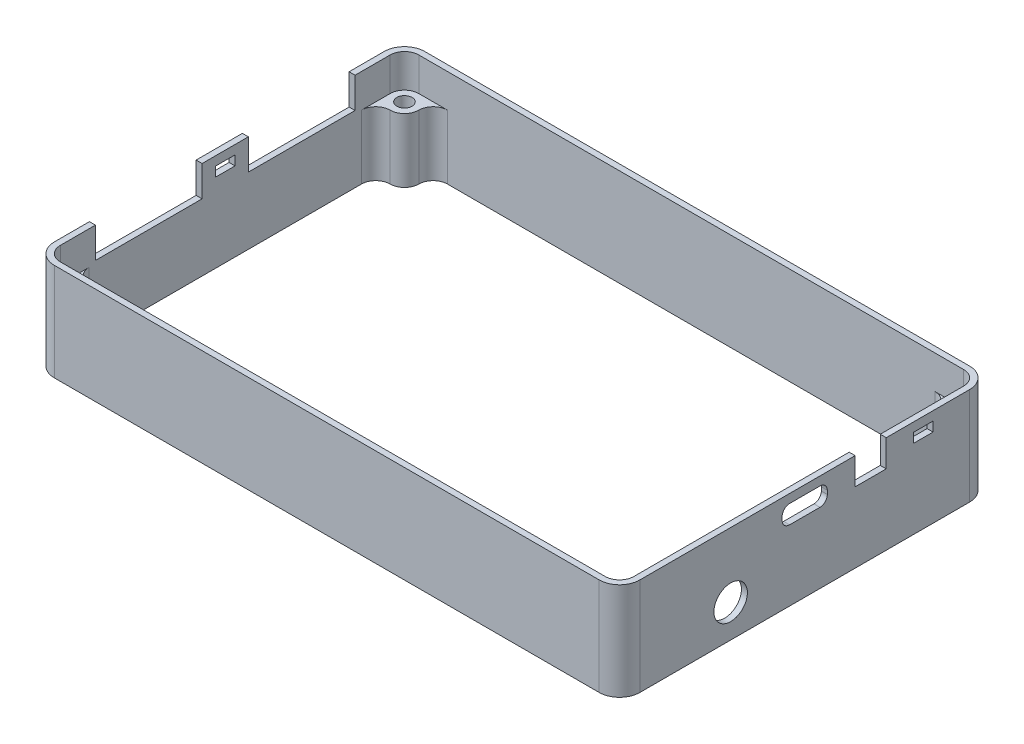
SolidWorks part; units mm, degrees
ref_plane "Front Plane" through (0, 0, 0) normal (0, 0, 1) x (1, 0, 0)
ref_plane "Top Plane" through (0, 0, 0) normal (0, 1, 0) x (1, 0, 0)
ref_plane "Right Plane" through (0, 0, 0) normal (1, 0, 0) x (0, 0, -1)
sketch "pcb" plane through (0, 0, 0) normal (0, 1, 0) x (1, 0, 0)
  line L0 (-14, -27.5) -> (-42, -27.5) construction
  line L1 (-57, -37.5) -> (57, -37.5)
  line L2 (-60, -34.5) -> (-60, 34.5)
  line L3 (-57, 37.5) -> (57, 37.5)
  line L4 (60, -34.5) -> (60, 34.5)
  line L5 (-60, -37.5) -> (60, 37.5) construction
  line L6 (-60, 37.5) -> (60, -37.5) construction
  line L7 (-14, -27.5) -> (14, -27.5) construction
  line L8 (14, -27.5) -> (42, -27.5) construction
  line L9 (-42, -27.5) -> (-60, -27.5) construction
  line L10 (42, -27.5) -> (60, -27.5) construction
  line L11 (-60, 0) -> (60, 0) construction
  line L13 (2.43, 12.5075) -> (10.05, 12.5075)
  line L14 (2.43, 12.5075) -> (2.43, 9.9675)
  line L15 (2.43, 9.9675) -> (10.05, 9.9675)
  line L16 (10.05, 12.5075) -> (10.05, 9.9675)
  arc A0 (-57, -37.5) -> (-60, -34.5) centre (-57, -34.5) cw
  arc A1 (57, -37.5) -> (60, -34.5) centre (57, -34.5) ccw
  arc A2 (57, 37.5) -> (60, 34.5) centre (57, 34.5) cw
  arc A3 (-60, 34.5) -> (-57, 37.5) centre (-57, 34.5) cw
  circle A4 centre (-57, 34.5) radius 1.6
  circle A5 centre (57, 34.5) radius 1.6
  circle A6 centre (57, -34.5) radius 1.6
  circle A7 centre (-57, -34.5) radius 1.6
  circle A8 centre (-42, -27.5) radius 5.5
  circle A9 centre (-14, -27.5) radius 5.5
  circle A10 centre (14, -27.5) radius 5.5
  circle A11 centre (42, -27.5) radius 5.5
  circle A12 centre (-42, 27.5) radius 5.5
  circle A13 centre (-14, 27.5) radius 5.5
  circle A14 centre (14, 27.5) radius 5.5
  circle A15 centre (42, 27.5) radius 5.5
  point P0 (0, 0)
  dimension "D3" = 3
  dimension "D4" = 3
  dimension "D5" = 3
  dimension "D6" = 3
  dimension "D7" = 3.2
  dimension "D9" = 11
  dimension "D10" = 18
  dimension "D1" = 120
  dimension "D2" = 75
  dimension "D8" = 10
  dimension "D11" = 62.43
  dimension "D12" = 47.4675
  dimension "D13" = 2.54
  dimension "D14" = 7.62
sketch "Sketch3" plane through (0, 0, 0) normal (0, 0, 1) x (1, 0, 0)
  line L0 (0, 0) -> (0, 1.6) construction
  line L1 (-57, 0) -> (57, 0) construction
  line L2 (0, 1.6) -> (0, 7) construction
  line L3 (0, 7) -> (0, 8.6) construction
  line L4 (0, 0) -> (0, -13.4) construction
  line L5 (0, -13.4) -> (0, -16.4) construction
  dimension "D1" = 1.6
  dimension "D2" = 3
  dimension "D3" = 13.4
  dimension "D4" = 5.4
  dimension "D5" = 1.6
  dimension "D6" = 25
sketch "Sketch2" plane through (0, 0, 0) normal (0, 1, 0) x (1, 0, 0)
  line L0 (-60, -34.5) -> (-60, 34.5) construction
  line L1 (-57, -37.5) -> (57, -37.5) construction
  line L2 (60, -34.5) -> (60, 34.5) construction
  line L3 (-57, 37.5) -> (57, 37.5) construction
  line L4 (-60, -34.5) -> (-60, 34.5)
  line L5 (-57, -37.5) -> (57, -37.5)
  line L6 (60, -34.5) -> (60, 34.5)
  line L7 (-57, 37.5) -> (57, 37.5)
  line L8 (-61.25, -34.5) -> (-61.25, 34.5)
  line L9 (-57, -38.75) -> (57, -38.75)
  line L10 (61.25, -34.5) -> (61.25, 34.5)
  line L11 (-57, 38.75) -> (57, 38.75)
  arc A0 (-57, 37.5) -> (-60, 34.5) centre (-57, 34.5) ccw construction
  arc A1 (-60, -34.5) -> (-57, -37.5) centre (-57, -34.5) ccw construction
  arc A2 (57, -37.5) -> (60, -34.5) centre (57, -34.5) ccw construction
  arc A3 (60, 34.5) -> (57, 37.5) centre (57, 34.5) ccw construction
  arc A4 (-57, 37.5) -> (-60, 34.5) centre (-57, 34.5) ccw
  arc A5 (-60, -34.5) -> (-57, -37.5) centre (-57, -34.5) ccw
  arc A6 (57, -37.5) -> (60, -34.5) centre (57, -34.5) ccw
  arc A7 (60, 34.5) -> (57, 37.5) centre (57, 34.5) ccw
  arc A8 (-57, 38.75) -> (-61.25, 34.5) centre (-57, 34.5) ccw
  arc A9 (-61.25, -34.5) -> (-57, -38.75) centre (-57, -34.5) ccw
  arc A10 (57, -38.75) -> (61.25, -34.5) centre (57, -34.5) ccw
  arc A11 (61.25, 34.5) -> (57, 38.75) centre (57, 34.5) ccw
  dimension "D1" = 1.25
extrude "Walls" add sketch "Sketch2" against normal up to vertex (13.4 mm away) and the other way up to vertex (7 mm away) up to point (0, -13.4, 0) other way up to point (0, 7, 0)
sketch "Sketch11" plane through (0, 0, 0) normal (0, 1, 0) x (1, 0, 0)
  line L0 (-60, -34.5) -> (-60, -31.5)
  line L1 (-60, -34.5) -> (-60, 34.5) construction
  line L2 (-60, -31.5) -> (-54, -31.5)
  line L3 (-54, -31.5) -> (-54, -37.5)
  line L4 (-57, -37.5) -> (57, -37.5) construction
  line L5 (-54, -37.5) -> (-57, -37.5)
  line L6 (-57, 37.5) -> (-54, 37.5)
  line L7 (-57, 37.5) -> (57, 37.5) construction
  line L8 (-54, 37.5) -> (-54, 31.5)
  line L9 (-54, 31.5) -> (-60, 31.5)
  line L10 (-60, 31.5) -> (-60, 34.5)
  line L11 (60, -31.5) -> (54, -31.5)
  line L12 (60, -34.5) -> (60, 34.5) construction
  line L13 (54, -31.5) -> (54, -37.5)
  line L14 (54, -37.5) -> (57, -37.5)
  line L15 (60, -31.5) -> (60, -34.5)
  line L16 (57, 37.5) -> (54, 37.5)
  line L17 (54, 37.5) -> (54, 31.5)
  line L18 (54, 31.5) -> (60, 31.5)
  line L19 (60, 31.5) -> (60, 34.5)
  arc A0 (-60, -34.5) -> (-57, -37.5) centre (-57, -34.5) ccw construction
  arc A1 (-60, -34.5) -> (-57, -37.5) centre (-57, -34.5) ccw
  arc A2 (-57, 37.5) -> (-60, 34.5) centre (-57, 34.5) ccw construction
  arc A3 (-57, 37.5) -> (-60, 34.5) centre (-57, 34.5) ccw
  circle A4 centre (-57, 34.5) radius 1.6 construction
  circle A5 centre (-57, 34.5) radius 1.6
  circle A6 centre (-57, -34.5) radius 1.6 construction
  circle A7 centre (-57, -34.5) radius 1.6
  arc A8 (57, -37.5) -> (60, -34.5) centre (57, -34.5) ccw construction
  arc A9 (57, -37.5) -> (60, -34.5) centre (57, -34.5) ccw
  circle A10 centre (57, -34.5) radius 1.6 construction
  circle A11 centre (57, -34.5) radius 1.6
  arc A12 (60, 34.5) -> (57, 37.5) centre (57, 34.5) ccw construction
  arc A13 (60, 34.5) -> (57, 37.5) centre (57, 34.5) ccw
  circle A14 centre (57, 34.5) radius 1.6 construction
  circle A15 centre (57, 34.5) radius 1.6
  dimension "D1" = 6
  dimension "D2" = 6
  dimension "D3" = 6
  dimension "D4" = 6
extrude "Boss-Extrude4" add sketch "Sketch11" against normal up to surface (13.4 mm away) up to face at (0, -13.4, 0)
fillet "Fillet1" radius 3 12 edges at (60, -6.7, -31.5) (54, -6.7, -37.5) (-54, -6.7, -37.5) (-60, -6.7, -31.5) (-54, -6.7, 37.5) (-60, -6.7, 31.5) (54, -6.7, 37.5) (60, -6.7, 31.5) (54, -6.7, 31.5) (-54, -6.7, 31.5) (-54, -6.7, -31.5) (54, -6.7, -31.5)
sketch "Sketch8" plane through (61.25, 0, 0) normal (1, 0, 0) x (0, 0, -1)
  line L0 (0, 1.6) -> (0, 7) construction
  line L1 (-3.17, 1.57) -> (3.17, 1.57)
  line L2 (-4.47, 2.87) -> (-4.47, 3.63)
  line L3 (-3.17, 4.93) -> (3.17, 4.93)
  line L4 (4.47, 2.87) -> (4.47, 3.63)
  line L5 (-4.47, 1.57) -> (4.47, 4.93) construction
  line L6 (-4.47, 4.93) -> (4.47, 1.57) construction
  line L8 (0, 0) -> (0, 1.6) construction
  line L9 (0, 0) -> (0, 1.6) construction
  line L11 (16.8, 1.6) -> (10.8, 1.6)
  line L12 (16.8, 1.6) -> (16.8, 6.82)
  line L13 (16.8, 6.82) -> (10.8, 6.82)
  line L14 (10.8, 1.6) -> (10.8, 6.82)
  line L15 (-37.5, 0) -> (37.5, 0) construction
  line L16 (0, 0) -> (0, -13.4) construction
  line L18 (23, 4.87) -> (26.6, 4.87)
  line L19 (23, 4.87) -> (23, 3.37)
  line L20 (23, 3.37) -> (26.6, 3.37)
  line L21 (26.6, 4.87) -> (26.6, 3.37)
  arc A0 (3.17, 4.93) -> (4.47, 3.63) centre (3.17, 3.63) cw
  arc A1 (3.17, 1.57) -> (4.47, 2.87) centre (3.17, 2.87) ccw
  arc A2 (-3.17, 1.57) -> (-4.47, 2.87) centre (-3.17, 2.87) cw
  arc A3 (-4.47, 3.63) -> (-3.17, 4.93) centre (-3.17, 3.63) cw
  circle A4 centre (-15.5, -6.55) radius 3.25
  point P0 (0, 3.25)
  point P10 (13.8, 1.6)
  dimension "D4" = 1.3
  dimension "D5" = 1.3
  dimension "D6" = 1.3
  dimension "D7" = 1.3
  dimension "D11" = 6.5
  dimension "D1" = 3.36
  dimension "D2" = 8.94
  dimension "D3" = 3.25
  dimension "D8" = 13.8
  dimension "D9" = 6
  dimension "D10" = 5.22
  dimension "D12" = 6.55
  dimension "D13" = 15.5
  dimension "D14" = 1.5
  dimension "D15" = 3.6
  dimension "D16" = 1.77
  dimension "D17" = 9.2
extrude "Cut-Extrude3" cut sketch "Sketch8" along direction (1, 0, 0) on the side against the normal up to surface (1.25 mm away) up to face at (60, -1.6, 0)
sketch "Sketch10" plane through (-61.25, 0, 0) normal (-1, 0, 0) x (0, 0, 1)
  line L0 (-34.5, 7) -> (34.5, 7) construction
  line L1 (5.84, 1.6) -> (26.16, 1.6)
  line L2 (5.84, 1.6) -> (5.84, 7)
  line L3 (5.84, 7) -> (26.16, 7)
  line L4 (26.16, 1.6) -> (26.16, 7)
  line L6 (-5.84, 1.6) -> (-26.16, 1.6)
  line L7 (-5.84, 1.6) -> (-5.84, 7)
  line L8 (-5.84, 7) -> (-26.16, 7)
  line L9 (-26.16, 1.6) -> (-26.16, 7)
  line L10 (0, 0) -> (0, 1.6) construction
  line L15 (0, 0) -> (0, 1.6) construction
  line L16 (-5.84, 1.6) -> (0, 1.6) construction
  line L17 (0, 1.6) -> (5.84, 1.6) construction
  line L22 (-1.8, 4.87) -> (1.8, 4.87)
  line L23 (-1.8, 4.87) -> (-1.8, 3.37)
  line L24 (-1.8, 3.37) -> (1.8, 3.37)
  line L25 (1.8, 4.87) -> (1.8, 3.37)
  point P10 (0, 3.37)
  dimension "D1" = 20.32
  dimension "D2" = 20.32
  dimension "D3" = 11.68
  dimension "D4" = 3.6
  dimension "D5" = 1.5
  dimension "D6" = 1.77
extrude "Cut-Extrude4" cut sketch "Sketch10" against normal up to next
other "Move Face3" flip direction yes face at (60.625, 4.12, -23) face at (60.625, 4.87, -24.8) face at (60.625, 4.12, -26.6) face at (60.625, 3.37, -24.8) offset 0.25 parameters "D1"=0.25
other "Move Face4" flip direction yes face at (60, -6.55, 12.25) face at (60.625, 2.0854, 3.9546) face at (60.625, 3.25, 4.47) face at (60.625, 4.4146, 3.9546) face at (60.625, 4.93, 0) face at (60.625, 2.0854, -3.9546) face at (60.625, 1.57, 0) face at (60.625, 3.25, -4.47) face at (60.625, 4.4146, -3.9546) face at (60.625, 1.6, -13.8) face at (60.625, 4.21, -16.8) face at (60.625, 4.21, -10.8) face at (60.625, 6.82, -13.8) offset 0.25 parameters "D1"=0.25
other "Move Face1" flip direction yes face at (-60.625, 4.3, 26.16) face at (-60.625, 1.6, 16) face at (-60.625, 4.3, 5.84) face at (-60.625, 4.3, -26.16) face at (-60.625, 1.6, -16) face at (-60.625, 4.3, -5.84) offset 1 parameters "D1"=1
other "Move Face2" flip direction yes face at (-60.625, 4.12, -1.8) face at (-60.625, 4.87, 0) face at (-60.625, 3.37, 0) face at (-60.625, 4.12, 1.8) offset 0.25 parameters "D1"=0.25
sketch "Sketch4" plane through (0, -13.4, 0) normal (0, -1, 0) x (1, 0, 0)
  line L4 (-57, -38.75) -> (57, -38.75)
  line L5 (61.25, -34.5) -> (61.25, 34.5)
  line L6 (57, 38.75) -> (-57, 38.75)
  line L7 (-61.25, 34.5) -> (-61.25, -34.5)
  line L8 (-57, -38.75) -> (57, -38.75)
  line L9 (61.25, -34.5) -> (61.25, 34.5)
  line L10 (57, 38.75) -> (-57, 38.75)
  line L11 (-61.25, 34.5) -> (-61.25, -34.5)
  circle A0 centre (57, -34.5) radius 2.15
  circle A1 centre (-57, -34.5) radius 2.15
  circle A2 centre (-57, 34.5) radius 2.15
  circle A3 centre (57, 34.5) radius 2.15
  arc A4 (-61.25, -34.5) -> (-57, -38.75) centre (-57, -34.5) ccw
  arc A5 (57, -38.75) -> (61.25, -34.5) centre (57, -34.5) ccw
  arc A6 (61.25, 34.5) -> (57, 38.75) centre (57, 34.5) ccw
  arc A7 (-57, 38.75) -> (-61.25, 34.5) centre (-57, 34.5) ccw
  arc A8 (-61.25, -34.5) -> (-57, -38.75) centre (-57, -34.5) ccw
  arc A9 (57, -38.75) -> (61.25, -34.5) centre (57, -34.5) ccw
  arc A10 (61.25, 34.5) -> (57, 38.75) centre (57, 34.5) ccw
  arc A11 (-57, 38.75) -> (-61.25, 34.5) centre (-57, 34.5) ccw
  dimension "D2" = 4.3
  dimension "D1" = 0
extrude "Bottom Lid" add sketch "Sketch4" along normal blind 3 separate body
sketch "Sketch5" plane through (0, 7, 0) normal (0, 1, 0) x (1, 0, 0)
  line L0 (2.43, 12.5075) -> (2.43, 9.9675) construction
  line L1 (2.43, 9.9675) -> (10.05, 9.9675) construction
  line L2 (2.43, 12.5075) -> (10.05, 12.5075) construction
  line L3 (10.05, 12.5075) -> (10.05, 9.9675) construction
  line L4 (57, 38.75) -> (-57, 38.75)
  line L5 (61.25, -34.5) -> (61.25, 34.5)
  line L6 (-57, -38.75) -> (57, -38.75)
  line L7 (-61.25, 34.5) -> (-61.25, -34.5)
  line L12 (57, 38.75) -> (-57, 38.75)
  line L13 (61.25, -34.5) -> (61.25, 34.5)
  line L14 (-57, -38.75) -> (57, -38.75)
  line L15 (-61.25, 34.5) -> (-61.25, -34.5)
  line L16 (2.43, 12.5075) -> (2.43, 9.9675)
  line L17 (2.43, 9.9675) -> (10.05, 9.9675)
  line L18 (2.43, 12.5075) -> (10.05, 12.5075)
  line L19 (10.05, 12.5075) -> (10.05, 9.9675)
  circle A3 centre (42, 27.5) radius 5.5 construction
  circle A15 centre (42, 27.5) radius 5.5
  circle A16 centre (-14, 27.5) radius 5.5 construction
  circle A17 centre (14, 27.5) radius 5.5 construction
  circle A18 centre (-14, 27.5) radius 5.5
  circle A19 centre (14, 27.5) radius 5.5
  circle A20 centre (-42, 27.5) radius 5.5 construction
  circle A21 centre (-42, 27.5) radius 5.5
  circle A22 centre (42, -27.5) radius 5.5 construction
  circle A23 centre (14, -27.5) radius 5.5 construction
  circle A24 centre (-14, -27.5) radius 5.5 construction
  circle A25 centre (-42, -27.5) radius 5.5 construction
  circle A26 centre (42, -27.5) radius 5.5
  circle A27 centre (14, -27.5) radius 5.5
  circle A28 centre (-14, -27.5) radius 5.5
  circle A29 centre (-42, -27.5) radius 5.5
  circle A30 centre (-57, -34.5) radius 1.6 construction
  circle A31 centre (-57, 34.5) radius 1.6 construction
  circle A32 centre (57, 34.5) radius 1.6 construction
  circle A33 centre (57, -34.5) radius 1.6 construction
  circle A34 centre (-57, -34.5) radius 1.6
  circle A35 centre (-57, 34.5) radius 1.6
  circle A36 centre (57, 34.5) radius 1.6
  circle A37 centre (57, -34.5) radius 1.6
  arc A38 (-57, 38.75) -> (-61.25, 34.5) centre (-57, 34.5) ccw
  arc A39 (61.25, 34.5) -> (57, 38.75) centre (57, 34.5) ccw
  arc A40 (57, -38.75) -> (61.25, -34.5) centre (57, -34.5) ccw
  arc A41 (-61.25, -34.5) -> (-57, -38.75) centre (-57, -34.5) ccw
  arc A42 (-57, 38.75) -> (-61.25, 34.5) centre (-57, 34.5) ccw
  arc A43 (61.25, 34.5) -> (57, 38.75) centre (57, 34.5) ccw
  arc A44 (57, -38.75) -> (61.25, -34.5) centre (57, -34.5) ccw
  arc A45 (-61.25, -34.5) -> (-57, -38.75) centre (-57, -34.5) ccw
  dimension "D1" = 0
extrude "Top Lid" add sketch "Sketch5" along normal blind 1.6 separate body
other "Move Face5" flip direction yes face at (2.43, 7.8, -11.2375) face at (6.24, 7.8, -9.9675) face at (10.05, 7.8, -11.2375) face at (6.24, 7.8, -12.5075) offset 0.25 parameters "D1"=0.25
delete or keep bodies "Body-Delete/Keep 1" type keep bodies bodies 120
delete or keep bodies "Body-Delete/Keep 2" [suppressed] type keep bodies bodies 124
delete or keep bodies "Body-Delete/Keep 3" [suppressed] type keep bodies bodies 102
other "Top Lid Offset" [suppressed] offset 0.0762 parameters "D1"=0.0762
other "Top Lid Offset 2" [suppressed] flip direction yes offset 0.1 parameters "D1"=0.1
other "Move Face6" [suppressed] offset 0.0762 parameters "D1"=0.0762
equation "\"D2@Sketch10\"=\"D1@Sketch10\""
equation "\"D2@Sketch11\"=\"D1@Sketch11\""
equation "\"D3@Sketch11\"=\"D1@Sketch11\""
equation "\"D4@Sketch11\"=\"D1@Sketch11\""
